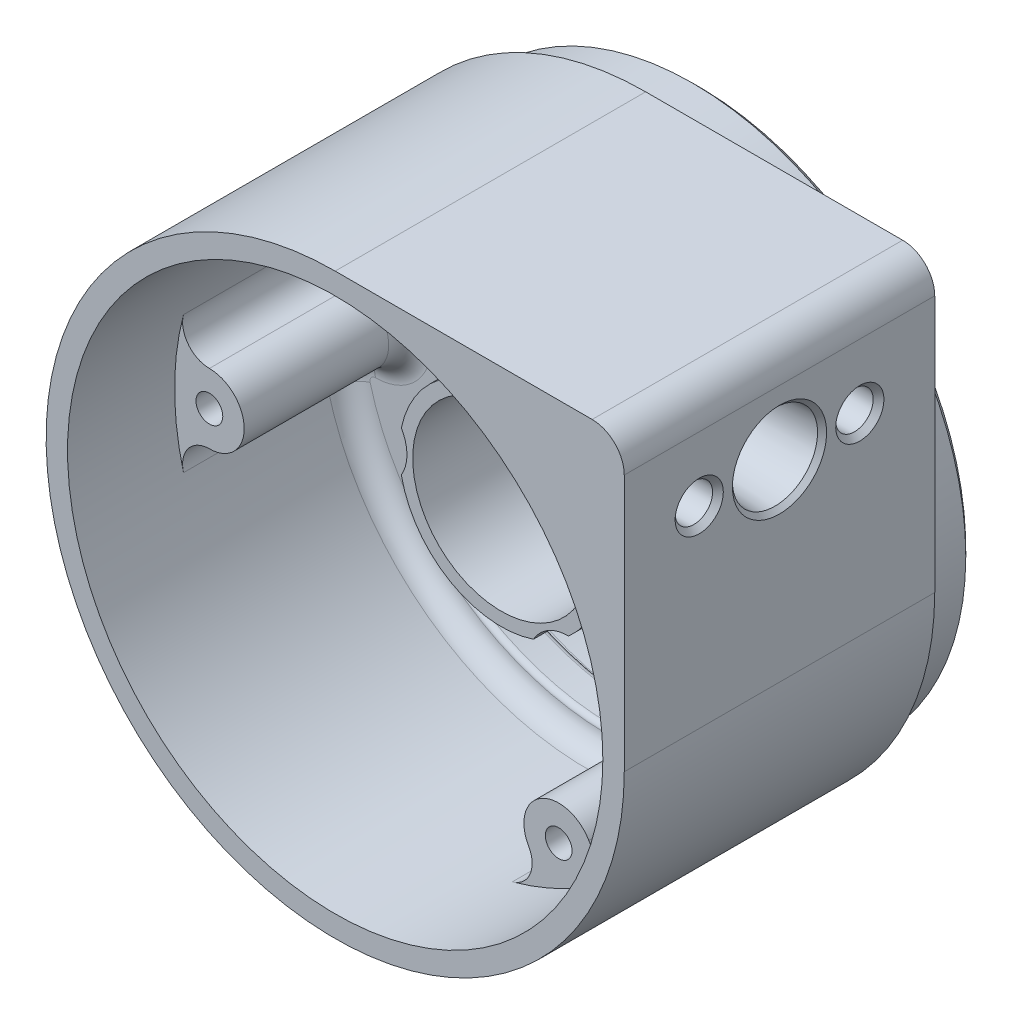
SolidWorks part; units mm, degrees
ref_plane "Front Plane" through (0, 0, 0) normal (0, 0, 1) x (1, 0, 0)
ref_plane "Top Plane" through (0, 0, 0) normal (0, 1, 0) x (1, 0, 0)
ref_plane "Right Plane" through (0, 0, 0) normal (1, 0, 0) x (0, 0, -1)
sketch "Sketch1" plane through (0, 0, 0) normal (0, 0, 1) x (1, 0, 0)
  line L0 (-12.5, 0) -> (0, 0) construction
  line L1 (0, 0) -> (6.25, 10.8253) construction
  line L2 (6.25, -10.8253) -> (0, 0) construction
  circle A0 centre (0, 0) radius 27
  circle A1 centre (0, 0) radius 12.5 construction
  circle A2 centre (0, 0) radius 7.75
  circle A3 centre (0, 0) radius 3 construction
  circle A4 centre (6.25, 10.8253) radius 2.25
  circle A5 centre (-12.5, 0) radius 2.25
  circle A6 centre (6.25, -10.8253) radius 2.25
  dimension "D1" = 54
  dimension "D2" = 6
  dimension "D3" = 15.5
  dimension "D4" = 25
  dimension "D7" = 4.5
  dimension "D5" = 120
  dimension "D6" = 120
extrude "Boss-Extrude1" add sketch "Sketch1" along normal blind 25
sketch "Sketch2" plane through (0, 0, 25) normal (0, 0, 1) x (1, 0, 0)
  circle A0 centre (6.25, 10.8253) radius 3.75
  circle A1 centre (6.25, -10.8253) radius 3.75
  circle A2 centre (-12.5, 0) radius 3.75
  dimension "D1" = 7.5
extrude "Cut-Extrude1" cut sketch "Sketch2" against normal offset from surface (20.5 mm away) 4.5 up to face at (27, 0, 0)
sketch "Sketch3" plane through (0, 0, 25) normal (0, 0, 1) x (1, 0, 0)
  line L0 (13.9654, 0) -> (0, 13.9654) construction
  line L1 (0, -17.6777) -> (17.6777, 0) construction
  line L2 (0, -17.6777) -> (-17.6777, 0) construction
  line L3 (-17.6777, 0) -> (0, 17.6777) construction
  line L4 (17.6777, 0) -> (0, 17.6777) construction
  line L5 (0, -17.6777) -> (0, 17.6777) construction
  line L6 (-17.6777, 0) -> (17.6777, 0) construction
  line L7 (0, 13.9654) -> (-13.9654, 0) construction
  line L8 (-13.9654, 0) -> (0, -13.9654) construction
  line L9 (0, -13.9654) -> (13.9654, 0) construction
  line L10 (-17.9605, 0) -> (0, 17.9605)
  line L11 (17.9605, 0) -> (0, 17.9605)
  line L12 (0, -17.9605) -> (17.9605, 0)
  line L13 (0, -17.9605) -> (-17.9605, 0)
  circle A0 centre (13.9654, 0) radius 1.625 construction
  circle A1 centre (0, -13.9654) radius 1.625 construction
  circle A2 centre (-13.9654, 0) radius 1.625 construction
  circle A3 centre (0, 13.9654) radius 1.625 construction
  point P0 (0, 0)
  dimension "D2" = 3.25
  dimension "D3" = 1
  dimension "D1" = 25
  dimension "D4" = 0.2
sketch "Sketch5" plane through (0, 0, 25) normal (0, 0, 1) x (1, 0, 0)
  line L0 (0, 27) -> (24, 27)
  line L3 (27, 0) -> (27, 24)
  circle A0 centre (0, 0) radius 27 construction
  arc A1 (0, 27) -> (27, 0) centre (0, 0) cw
  arc A3 (24, 27) -> (27, 24) centre (24, 24) cw
  circle M11 centre (0, 0) radius 27
extrude "Boss-Extrude2" add sketch "Sketch5" against normal up to surface (25 mm away) contours A3 L0 M11 | M11 region at (20.9021, 20.9021, 25) up to face at (27, 0, 0)
sketch "Sketch8" plane through (0, 0, 0) normal (0, 0, -1) x (-1, 0, 0)
  circle A0 centre (0, 0) radius 8.625
  dimension "D1" = 17.25
extrude "Cut-Extrude5" cut sketch "Sketch8" against normal blind 2
chamfer "Chamfer2" distance 1 angle 72 1 edges at (-7.75, 0, 2) first distance on face at (-7.75, 0, 2)
sketch "Sketch9" plane through (0, 0, 25) normal (0, 0, 1) x (1, 0, 0)
  circle A0 centre (0, 0) radius 25
  dimension "D1" = 50
extrude "Cut-Extrude6" cut sketch "Sketch9" against normal offset from surface (21.5 mm away) 3.5 up to face at (-8.625, 0, 0)
sketch "Sketch10" plane through (0, 0, 3.5) normal (0, 0, 1) x (1, 0, 0)
  line L0 (0, 0) -> (11.1505, 11.1233) construction
  line L1 (0, 0) -> (4.0578, -15.2183) construction
  line L2 (0, 0) -> (-15.2083, 4.095) construction
  line L3 (0, 0) -> (-2.716, 15.5141) construction
  line L4 (0, 0) -> (-12.0776, -10.1091) construction
  line L5 (0, 0) -> (13.8224, -5.0501) construction
  line L6 (-14.21, 3.8262) -> (-12.2736, 3.3048)
  line L7 (-2.1919, 12.5203) -> (-2.5377, 14.4956)
  line L8 (10.4185, 10.3931) -> (8.9988, 8.9768)
  line L9 (11.9388, -4.3619) -> (14.7936, -5.4049)
  line L10 (3.7914, -14.2193) -> (3.2748, -12.2816)
  line L11 (-9.747, -8.1584) -> (-11.2847, -9.4455)
  circle A0 centre (0, 0) radius 15.75 construction
  circle A1 centre (0, 0) radius 11.75 construction
  circle A2 centre (6.25, 10.8253) radius 2.25 construction
  arc A3 (-1.6579, 15.6625) -> (10.3708, 11.8537) centre (0, 0) cw
  arc A4 (14.3931, -6.3954) -> (5.0802, -14.9082) centre (0, 0) cw
  arc A5 (-15.451, 3.0545) -> (-12.7351, -9.2671) centre (0, 0) ccw
  arc A6 (-11.0713, 3.9355) -> (-2.9277, 11.3794) centre (0, 0) cw
  arc A7 (8.9439, 7.6203) -> (11.3187, -3.1542) centre (0, 0) cw
  arc A8 (2.1275, -11.5558) -> (-8.391, -8.2252) centre (0, 0) cw
  arc A9 (-8.391, -8.2252) -> (-9.747, -8.1584) centre (-9.1051, -8.9252) ccw
  arc A10 (2.1275, -11.5558) -> (3.2748, -12.2816) centre (2.3085, -12.5393) cw
  arc A11 (3.7914, -14.2193) -> (5.0802, -14.9082) centre (4.7577, -13.9616) ccw
  arc A12 (11.3187, -3.1542) -> (11.9388, -4.3619) centre (12.282, -3.4227) ccw
  arc A13 (14.3931, -6.3954) -> (13.8224, -5.0501) centre (13.4792, -5.9894) ccw
  arc A14 (8.9439, 7.6203) -> (8.9988, 8.9768) centre (9.7051, 8.2689) cw
  arc A15 (10.4185, 10.3931) -> (10.3708, 11.8537) centre (9.7123, 11.1011) ccw
  arc A16 (-2.5377, 14.4956) -> (-1.6579, 15.6625) centre (-1.5527, 14.6681) cw
  arc A17 (-2.9277, 11.3794) -> (-2.1919, 12.5203) centre (-3.1769, 12.3479) ccw
  arc A18 (-11.0713, 3.9355) -> (-12.2736, 3.3048) centre (-12.0136, 4.2704) cw
  arc A19 (-14.21, 3.8262) -> (-15.451, 3.0545) centre (-14.47, 2.8606) ccw
  arc A20 (-12.7351, -9.2671) -> (-11.2847, -9.4455) centre (-11.9266, -8.6787) ccw
  point P23 (-9.0103, -7.5417)
  point P26 (3.0272, -11.3533)
  point P31 (11.0365, -4.0322)
  point P37 (8.3187, 8.2983)
  point P46 (-2.0262, 11.574)
  point P49 (-11.3459, 3.055)
  dimension "D1" = 23.5
  dimension "D2" = 31.5
  dimension "D6" = 55
  dimension "D9" = 1
  dimension "D3" = 120
  dimension "D4" = 120
  dimension "D5" = 1
  dimension "D7" = 55
  dimension "D8" = 55
sketch "Sketch11" plane through (0, 0, 3.5) normal (0, 0, 1) x (1, 0, 0)
  line L0 (-3.3134, 13.3589) -> (-5.2425, 21.1366)
  line L1 (-13.0084, 4.4969) -> (-20.5819, 7.1151)
  line L2 (10.3986, 9.0171) -> (16.4528, 14.2669)
  line L3 (-14.21, 3.8262) -> (-12.2736, 3.3048) construction
  line L4 (-2.1919, 12.5203) -> (-2.5377, 14.4956) construction
  line L5 (13.2259, -3.81) -> (20.9261, -6.0282)
  line L6 (2.6097, -13.514) -> (4.1291, -21.382)
  line L7 (-9.9125, -9.549) -> (-15.6836, -15.1084)
  line L8 (0, 0) -> (-3.9736, 12.1676) construction
  line L9 (0, 0) -> (12.5242, -2.6426) construction
  arc A0 (-3.9736, 12.1676) -> (-11.7627, 5.0477) centre (0, 0) ccw
  circle A1 centre (0, 0) radius 25 construction
  arc A2 (-21.1843, 8.4299) -> (-20.5819, 7.1151) centre (-20.2552, 8.0602) ccw
  arc A3 (-6.4981, 21.8544) -> (-21.1843, 8.4299) centre (0, 0) ccw
  arc A4 (-11.7627, 5.0477) -> (-13.0084, 4.4969) centre (-12.6816, 5.4421) cw
  arc A5 (-3.9736, 12.1676) -> (-3.3134, 13.3589) centre (-4.284, 13.1182) ccw
  arc A6 (-5.2425, 21.1366) -> (-6.4981, 21.8544) centre (-6.2131, 20.8959) ccw
  arc A7 (10.2528, 7.6629) -> (10.3986, 9.0171) centre (11.0538, 8.2616) cw
  arc A8 (17.8927, 14.1312) -> (16.4528, 14.2669) centre (17.1079, 13.5114) ccw
  arc A9 (22.1755, -5.2997) -> (17.8927, 14.1312) centre (0, 0) ccw
  arc A10 (20.9261, -6.0282) -> (22.1755, -5.2997) centre (21.2029, -5.0672) ccw
  arc A11 (12.5242, -2.6426) -> (13.2259, -3.81) centre (13.5027, -2.849) ccw
  arc A12 (12.5242, -2.6426) -> (10.2528, 7.6629) centre (0, 0) ccw
  arc A13 (1.5099, -12.7106) -> (2.6097, -13.514) centre (1.6279, -13.7037) cw
  arc A14 (3.2916, -22.5611) -> (4.1291, -21.382) centre (3.1473, -21.5716) ccw
  arc A15 (-15.6774, -16.5547) -> (3.2916, -22.5611) centre (0, 0) ccw
  arc A16 (-15.6836, -15.1084) -> (-15.6774, -16.5547) centre (-14.9898, -15.8286) ccw
  arc A17 (-8.5507, -9.525) -> (-9.9125, -9.549) centre (-9.2187, -10.2692) ccw
  arc A18 (-8.5507, -9.525) -> (1.5099, -12.7106) centre (0, 0) ccw
  dimension "D3" = 10
  dimension "D4" = 2.2
  dimension "D5" = 1
  dimension "D1" = 4
  dimension "D2" = 4
  dimension "D6" = 120
extrude "Cut-Extrude7" cut sketch "Sketch11" against normal through all
sketch "Sketch13" plane through (0, 0, 0) normal (0, 0, -1) x (-1, 0, 0)
  circle A0 centre (0, 0) radius 24.2
  arc A1 (-27, 0) -> (0, 27) centre (0, 0) ccw construction
  circle A2 centre (0, 0) radius 25.5
  dimension "D1" = 2.8
  dimension "D2" = 1.5
extrude "Boss-Extrude3" add sketch "Sketch13" along normal blind 5
fillet "Fillet2" radius 1 1 edges at (-24.2, 0, 0)
chamfer "Chamfer3" distance 0.6 angle 45 1 edges at (-25.5, 0, -5)
sketch "Sketch14" plane through (0, 0, 3.5) normal (0, 0, 1) x (1, 0, 0)
  line L0 (0, 0) -> (-25, 0) construction
  line L1 (0, 0) -> (12.5, 21.6506) construction
  line L2 (0, 0) -> (12.5, -21.6506) construction
  circle A0 centre (0, 0) radius 25 construction
  circle A1 centre (0, 0) radius 25 construction
  circle A2 centre (6.25, -10.8253) radius 2.25 construction
  circle A3 centre (6.25, -10.8253) radius 2.25 construction
  circle A4 centre (6.25, 10.8253) radius 2.25 construction
  circle A5 centre (-12.5, 0) radius 2.25 construction
  circle A6 centre (6.25, 10.8253) radius 2.25 construction
  circle A7 centre (-12.5, 0) radius 2.25 construction
  circle A8 centre (-21.75, 0) radius 3.25 construction
  arc A9 (-21.75, 3.25) -> (-24.169, 6.392) centre (-21.75, 5.7522) cw
  arc A10 (-21.75, -3.25) -> (-24.169, -6.392) centre (-21.75, -5.7522) ccw
  arc A11 (-21.75, 3.25) -> (-21.75, -3.25) centre (-21.75, 0) cw
  arc A12 (-24.169, 6.392) -> (-24.169, -6.392) centre (0, 0) ccw
  arc A13 (13.6896, 17.2111) -> (17.6201, 17.735) centre (15.8566, 15.9599) cw
  arc A14 (8.0604, 20.4611) -> (6.5489, 24.127) centre (5.8934, 21.7122) ccw
  arc A15 (13.6896, 17.2111) -> (8.0604, 20.4611) centre (10.875, 18.8361) cw
  arc A16 (17.6201, 17.735) -> (6.5489, 24.127) centre (0, 0) ccw
  circle A17 centre (10.875, 18.8361) radius 3.25 construction
  arc A18 (8.0604, -20.4611) -> (6.5489, -24.127) centre (5.8934, -21.7122) cw
  arc A19 (13.6896, -17.2111) -> (17.6201, -17.735) centre (15.8566, -15.9599) ccw
  arc A20 (8.0604, -20.4611) -> (13.6896, -17.2111) centre (10.875, -18.8361) cw
  arc A21 (6.5489, -24.127) -> (17.6201, -17.735) centre (0, 0) ccw
  circle A22 centre (10.875, -18.8361) radius 3.25 construction
  circle A23 centre (-21.75, 0) radius 1.25
  circle A24 centre (10.875, -18.8361) radius 1.25
  circle A25 centre (10.875, 18.8361) radius 1.25
  point P49 (0, 0)
  dimension "D1" = 6.5
  dimension "D3" = 2.5
  dimension "D2" = 3
extrude "Boss-Extrude4" add sketch "Sketch14" along normal offset from surface (15.5 mm away) 6 up to face at (25, 0, 25)
fillet "Fillet4" radius 2 12 edges at (8.2067, 22.666, 3.5) (-12.5, 21.6506, 3.5) (-23.7327, 4.2257, 3.5) (-18.5, 0, 3.5) (-23.7327, -4.2257, 3.5) (-12.5, -21.6506, 3.5) (8.2067, -22.666, 3.5) (9.25, -16.0215, 3.5) (15.5259, -18.4402, 3.5) (25, 0, 3.5) (15.5259, 18.4402, 3.5) (9.25, 16.0215, 3.5)
sketch "Sketch16" plane through (0, 0, 25) normal (0, 0, 1) x (1, 0, 0)
  line L2 (27, 0) -> (27, 24)
  line L3 (24, 27) -> (0, 27)
  line L4 (27, 0) -> (27, 24)
  line L5 (24, 27) -> (0, 27)
  circle A0 centre (0, 0) radius 25 construction
  circle A1 centre (0, 0) radius 25
  arc A2 (0, 27) -> (27, 0) centre (0, 0) ccw
  arc A3 (27, 24) -> (24, 27) centre (24, 24) ccw
  arc A4 (0, 27) -> (27, 0) centre (0, 0) ccw
  arc A5 (27, 24) -> (24, 27) centre (24, 24) ccw
  dimension "D1" = 0
extrude "Boss-Extrude5" add sketch "Sketch16" along normal blind 4
sketch "Sketch6" plane through (27, 0, 0) normal (1, 0, 0) x (0, 0, -1)
  line L0 (-14.5, 27) -> (-14.5, -27) construction
  line L3 (0, 27) -> (-29, 27) construction
  line L5 (-29, -27) -> (0, -27) construction
  circle A0 centre (-14.5, 18) radius 4
  dimension "D1" = 8
  dimension "D2" = 9
extrude "Cut-Extrude4" cut sketch "Sketch6" against normal blind 6 draft 3
fillet "Fillet3" radius 1 1 edges at (25.5, 0, 0)
sketch "Sketch17" plane through (27, 0, 0) normal (1, 0, 0) x (0, 0, -1)
  line L0 (-29, 18) -> (0, 18) construction
  line L1 (-29, 0) -> (-29, 24) construction
  line L2 (0, 24) -> (0, 0) construction
  line L3 (-22, 18) -> (-7, 18) construction
  circle A2 centre (-14.5, 18) radius 4 construction
  circle A3 centre (-14.5, 18) radius 4 construction
  circle A4 centre (-22, 18) radius 1.75
  circle A5 centre (-7, 18) radius 1.75
  point P13 (-14.5, 18)
  dimension "D1" = 3.5
  dimension "D2" = 15
extrude "Cut-Extrude8" cut sketch "Sketch17" against normal blind 5
chamfer "Chamfer4" distance 1 angle 45 2 edges at (22, 19.75, 7) (22, 19.75, 22)
chamfer "Chamfer5" distance 0.5 angle 45 2 edges at (27, 19.75, 22) (27, 19.75, 7)
chamfer "Chamfer6" distance 0.4 angle 45 1 edges at (27, 22, 14.5) first distance on face at (27, 20.25, 22)
sketch "Sketch18" plane through (0, 0, 3.5) normal (0, 0, 1) x (1, 0, 0)
  circle A0 centre (0, 0) radius 8.2626 construction
  circle A1 centre (0, 0) radius 8.2626
  circle A2 centre (0, 0) radius 9.5126 construction
  circle A3 centre (-12.5, 0) radius 3.7 construction
  circle A4 centre (6.25, -10.8253) radius 3.7 construction
  circle A5 centre (6.25, 10.8253) radius 3.7 construction
  arc A6 (-9.322, -1.8948) -> (3.02, -9.0205) centre (0, 0) ccw
  arc A7 (-9.322, -1.8948) -> (-9.322, 1.8948) centre (-12.5, 0) ccw
  arc A8 (-9.322, 1.8948) -> (3.02, 9.0205) centre (0, 0) cw
  arc A9 (3.02, 9.0205) -> (6.302, 7.1257) centre (6.25, 10.8253) ccw
  arc A10 (6.302, 7.1257) -> (6.302, -7.1257) centre (0, 0) cw
  arc A11 (6.302, -7.1257) -> (3.02, -9.0205) centre (6.25, -10.8253) ccw
  dimension "D1" = 1.25
  dimension "D2" = 7.4
extrude "Boss-Extrude6" add sketch "Sketch18" along normal blind 10
fillet "Fillet5" radius 1.5 3 edges at (9.5126, 0, 3.5) (-4.7563, 8.2382, 3.5) (-4.7563, -8.2382, 3.5)
sketch "Sketch20" plane through (0, 0, 3.5) normal (0, 0, 1) x (1, 0, 0)
  circle A0 centre (0, 0) radius 25 construction
  circle A1 centre (0, 0) radius 25
extrude "Boss-Extrude7" [suppressed] add sketch "Sketch20" against normal blind 0.2
sketch "Sketch19" plane through (0, 0, 19) normal (0, 0, 1) x (1, 0, 0)
  circle A0 centre (-21.75, 0) radius 1.25 construction
  circle A1 centre (10.875, -18.8361) radius 1.25 construction
  circle A2 centre (10.875, 18.8361) radius 1.25 construction
  circle A3 centre (-21.75, 0) radius 1.25
  circle A4 centre (10.875, -18.8361) radius 1.25
  circle A5 centre (10.875, 18.8361) radius 1.25
extrude "Cut-Extrude9" cut sketch "Sketch19" against normal through all
fillet "Fillet6" radius 0.5 48 edges at (17.2018, 14.507, 3.5) (22.2656, 4.9076, 3.5) (21.7066, -5.9311, 3.5) (17.076, -4.9191, 3.5) (12.6456, -3.3642, 3.5) (12.5, 2.7551, 3.5) (10.0595, 8.3687, 3.5) (-9.2363, -9.2693, 3.5) (-3.864, -12.2029, 3.5) (2.2177, -12.8962, 3.5) (3.3694, -17.448, 3.5) (3.9625, -22.1507, 3.5) (-6.8827, -21.7363, 3.5) (-15.9898, -15.8329, 3.5) (-5.7168, 21.764, 3.5) (-4.278, 17.2478, 3.5) (-3.4093, 12.6335, 3.5) (-8.636, 9.4477, 3.5) (-12.2773, 4.5275, 3.5) (-16.7951, 5.806, 3.5) (-21.1643, 7.6437, 3.5) (-3.4093, 12.6335, 0) (-8.636, 9.4477, 0) (-12.2773, 4.5275, 0) (-16.7951, 5.806, 0) (-21.1643, 7.6437, 0) (-15.3829, 16.8287, 0) (-5.7168, 21.764, 0) (3.9625, -22.1507, 0) (-6.8827, -21.7363, 0) (-15.9898, -15.8329, 0) (-12.798, -12.3287, 0) (-9.2363, -9.2693, 0) (-3.864, -12.2029, 0) (2.2177, -12.8962, 0) (10.0595, 8.3687, 0) (13.4257, 11.642, 0) (17.2018, 14.507, 0) (22.2656, 4.9076, 0) (21.7066, -5.9311, 0) (17.076, -4.9191, 0) (12.6456, -3.3642, 0) (13.4257, 11.642, 3.5) (-12.798, -12.3287, 3.5) (-15.3829, 16.8287, 3.5) (-4.278, 17.2478, 0) (3.3694, -17.448, 0) (12.5, 2.7551, 0)
